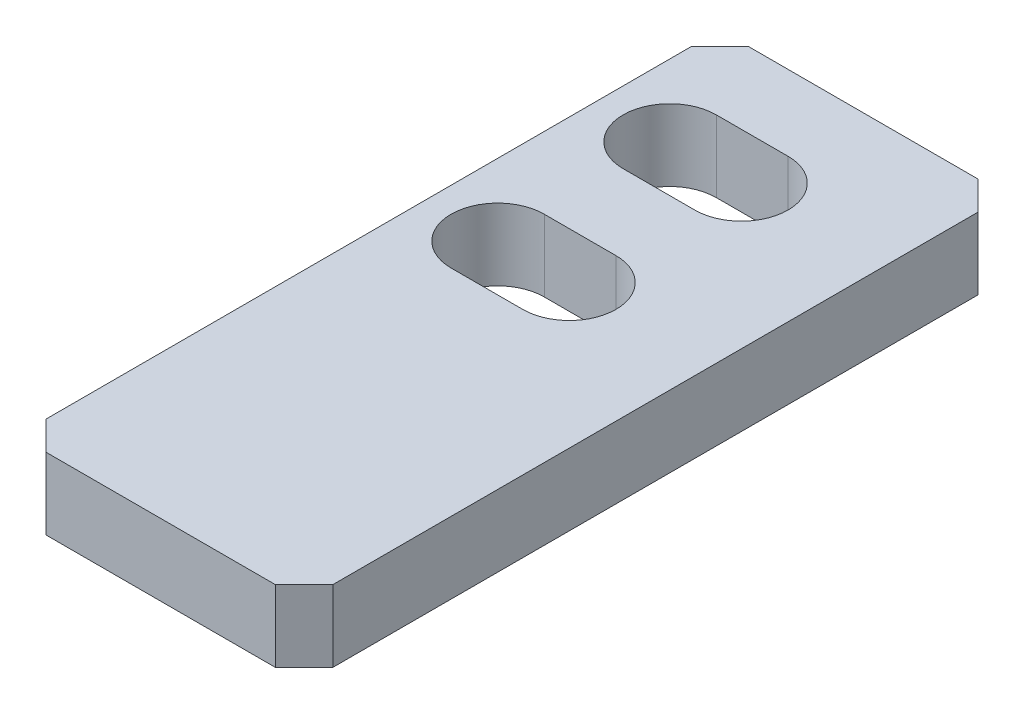
SolidWorks part; units mm, degrees
ref_plane "Front Plane" through (0, 0, 0) normal (0, 0, 1) x (1, 0, 0)
ref_plane "Top Plane" through (0, 0, 0) normal (0, 1, 0) x (1, 0, 0)
ref_plane "Right Plane" through (0, 0, 0) normal (1, 0, 0) x (0, 0, -1)
sketch "Sketch1" plane through (0, 0, 0) normal (0, 1, 0) x (1, 0, 0)
  line L0 (0, 47) -> (2, 49)
  line L1 (2, 0) -> (18, 0)
  line L2 (0, 2) -> (0, 47)
  line L3 (2, 49) -> (18, 49)
  line L4 (20, 2) -> (20, 47)
  line L5 (18, 49) -> (20, 47)
  line L6 (0, 2) -> (2, 0)
  line L7 (18, 0) -> (20, 2)
  line L8 (10, 40.5) -> (5, 40.5) construction
  line L9 (10, 37.25) -> (5, 37.25)
  line L10 (10, 43.75) -> (5, 43.75)
  line L11 (5, 28.5) -> (10, 28.5) construction
  line L12 (5, 31.75) -> (10, 31.75)
  line L13 (5, 25.25) -> (10, 25.25)
  arc A0 (10, 37.25) -> (10, 43.75) centre (10, 40.5) ccw
  arc A1 (5, 43.75) -> (5, 37.25) centre (5, 40.5) ccw
  arc A2 (5, 31.75) -> (5, 25.25) centre (5, 28.5) ccw
  arc A3 (10, 25.25) -> (10, 31.75) centre (10, 28.5) ccw
  point P0 (0, 0)
  point P1 (20, 49)
  point P2 (0, 49)
  point P3 (20, 0)
  point P15 (7.5, 40.5)
  point P20 (7.5, 28.5)
  point P27 (9.7542, 41.982)
  point P28 (0, 0)
  point P29 (0, 0)
  point P30 (10, 49)
  point P31 (0, 0)
  point P32 (0, 0)
  dimension "D1" = 49
  dimension "D2" = 20
  dimension "D3" = 2
  dimension "D4" = 45
  dimension "D5" = 2
  dimension "D6" = 45
  dimension "D7" = 2
  dimension "D8" = 45
  dimension "D9" = 2
  dimension "D10" = 45
  dimension "D11" = 5
  dimension "D12" = 8.5
  dimension "D13" = 12
  dimension "D14" = 6.5
  dimension "D15" = 6.5
extrude "Boss-Extrude1" add sketch "Sketch1" along normal blind 5 contours L4 L5 L3 L0 L2 L6 L1 L7
extrude "Cut-Extrude5" cut sketch "Sketch1<5>" along normal blind 5 flip side to cut
sketch "Sketch1<5>" plane through (0, 0, 0) normal (0, 1, 0) x (1, 0, 0) same geometry as "Sketch1"
